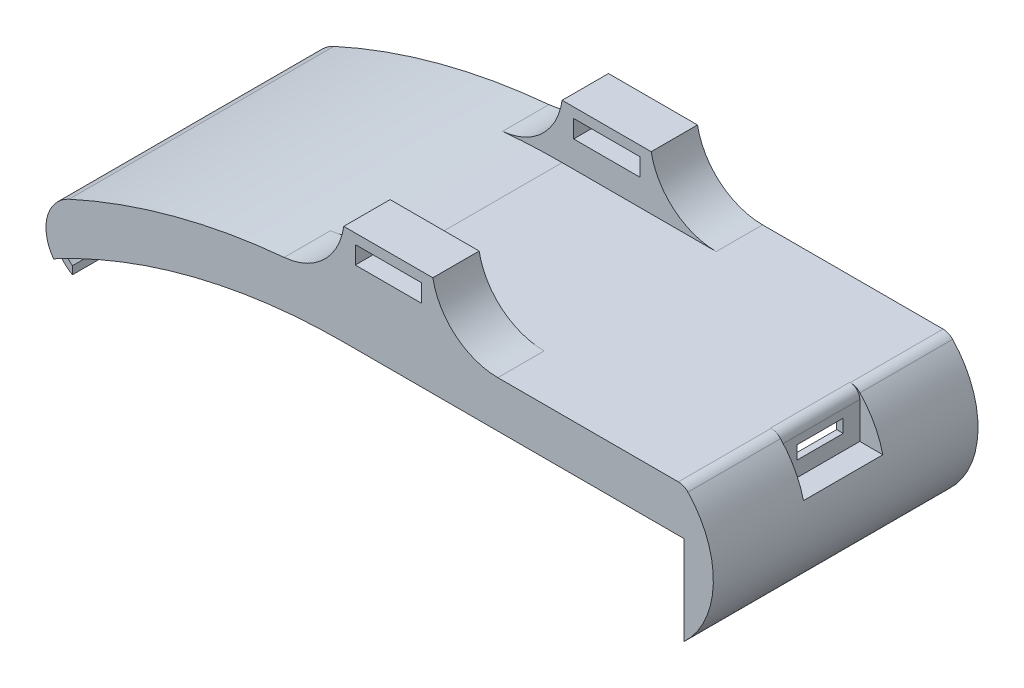
SolidWorks part; units mm, degrees
material "PLA"
ref_plane "Front Plane" through (0, 0, 0) normal (0, 0, 1) x (1, 0, 0)
ref_plane "Top Plane" through (0, 0, 0) normal (0, 1, 0) x (1, 0, 0)
ref_plane "Right Plane" through (0, 0, 0) normal (1, 0, 0) x (0, 0, -1)
sketch "Sketch1" plane through (0, 0, 0) normal (0, 0, 1) x (1, 0, 0)
  line L0 (93.6716, -39.9694) -> (93.6716, -40.9694)
  line L1 (3.6716, -40.9694) -> (3.6716, -39.9694)
  line L2 (3.6716, -39.9694) -> (-32.9868, -39.9694) construction
  line L3 (93.6716, -40.9694) -> (94.0742, -40.9694)
  line L4 (93.6271, -20.4794) -> (94.053, -20.4794)
  line L7 (93.6516, -21.4794) -> (42.6716, -21.4794)
  line L8 (93.6482, -40.9694) -> (93.6716, -40.9694)
  line L9 (93.6271, -20.4794) -> (42.6716, -20.4794)
  line L17 (93.6482, -40.9694) -> (3.6716, -40.9694) construction
  line L19 (93.6716, -39.9694) -> (3.6716, -39.9694) construction
  arc A0 (93.6516, -21.4794) -> (93.6716, -39.9694) centre (94.1163, -30.7239) cw construction
  arc A1 (42.6716, -21.4794) -> (1.5932, -30.4219) centre (42.6716, -120.3004) ccw
  arc A2 (1.5932, -30.4219) -> (3.6716, -39.9694) centre (3.6716, -34.9694) ccw
  arc A3 (93.6271, -20.4794) -> (93.6482, -40.9694) centre (94.1163, -30.7239) cw construction
  arc A4 (1.1775, -29.5124) -> (3.6716, -40.9694) centre (3.6716, -34.9694) ccw
  arc A5 (42.6716, -20.4794) -> (1.1775, -29.5124) centre (42.6716, -120.3004) ccw
  arc A6 (93.6516, -21.4794) -> (93.6716, -39.9694) centre (94.1163, -30.7239) cw construction
  arc A7 (93.6716, -39.9694) -> (93.6516, -21.4794) centre (84.5221, -30.7343) ccw
  arc A8 (94.0742, -40.9694) -> (94.053, -20.4794) centre (84.5221, -30.7343) ccw
  arc A9 (94.3754, -40.6798) -> (94.3539, -20.7675) centre (84.5221, -30.7343) ccw construction
  dimension "D9" = 5
  dimension "D6" = 13
  dimension "D2" = 1
  dimension "D3" = 50.98
  dimension "D4" = 19.49
  dimension "D5" = 90
  dimension "D7" = 1
  dimension "D8" = 39
  dimension "D1" = 1
extrude "Boss-Extrude1" add sketch "Sketch1" along normal blind 38 contours L9 A5 A4 A2 A1 L7 A0 L8 A3 region at (97.6251, -30.7201, 0)
sketch "Sketch2" plane through (0, 0, 0) normal (0, 0, -1) x (-1, 0, 0)
  line L0 (-93.6716, -40.9694) -> (-3.6716, -40.9694)
  line L6 (-93.6716, -40.9694) -> (-93.6716, -39.9694)
  line L7 (-94.0742, -40.9694) -> (-93.6716, -40.9694)
  line L8 (-42.6716, -20.4794) -> (-94.053, -20.4794)
  line L9 (-94.0742, -40.9694) -> (-93.6716, -40.9694)
  line L10 (-3.6716, -39.9694) -> (-3.6716, -40.9694)
  line L12 (-93.6516, -21.4794) -> (-42.6716, -21.4794)
  line L16 (-42.6716, -20.4794) -> (-94.053, -20.4794)
  arc A6 (-93.6516, -21.4794) -> (-93.6716, -39.9694) centre (-84.5221, -30.7343) ccw
  arc A8 (-1.5932, -30.4219) -> (-42.6716, -21.4794) centre (-42.6716, -120.3004) ccw
  arc A9 (-3.6716, -39.9694) -> (-1.5932, -30.4219) centre (-3.6716, -34.9694) ccw
  arc A10 (-3.6716, -40.9694) -> (-1.1775, -29.5124) centre (-3.6716, -34.9694) ccw
  arc A11 (-1.1775, -29.5124) -> (-42.6716, -20.4794) centre (-42.6716, -120.3004) ccw
  arc A12 (-94.053, -20.4794) -> (-94.0742, -40.9694) centre (-84.5221, -30.7343) ccw
  arc A13 (-94.053, -20.4794) -> (-94.0742, -40.9694) centre (-84.5221, -30.7343) ccw
  arc A16 (-3.6716, -40.9694) -> (-1.1775, -29.5124) centre (-3.6716, -34.9694) ccw
  arc A17 (-1.1775, -29.5124) -> (-42.6716, -20.4794) centre (-42.6716, -120.3004) ccw
  dimension "D1" = 0
extrude "Boss-Extrude2" add sketch "Sketch2" along normal blind 1
ref_plane "Plane1" through (0, 0, 19) normal (0, 0, 1) x (1, 0, 0)
mirror "Mirror1" about plane through (0, 0, 19) normal (0, 0, 1) of "Boss-Extrude2"
sketch "Sketch5" plane through (0, -21.4794, 0) normal (0, -1, 0) x (1, 0, 0)
  line L0 (42.6716, 38) -> (42.6716, 0) construction
  line L1 (45.3016, 27.89) -> (45.3016, 10.11) construction
  circle A0 centre (45.3016, 27.89) radius 1.5
  circle A1 centre (45.3016, 10.11) radius 1.5
  circle A2 centre (91.0216, 27.89) radius 1.5
  circle A3 centre (91.0216, 10.11) radius 1.5
  point P6 (42.6716, 19)
  point P7 (45.3016, 19)
  dimension "D3" = 3
  dimension "D1" = 2.63
  dimension "D2" = 17.78
  dimension "D4" = 2
extrude "Boss-Extrude4" add sketch "Sketch5" along normal blind 2
sketch "Sketch6" plane through (0.0001, -40.9694, 0) normal (0, -1, 0) x (1, 0, 0)
  line L0 (3.6715, 38) -> (3.6715, 0) construction
  line L2 (3.6715, 31.5) -> (-0.3285, 31.5)
  line L3 (3.6715, 31.5) -> (3.6715, 6.5)
  line L4 (3.6715, 6.5) -> (-0.3285, 6.5)
  line L5 (-0.3285, 31.5) -> (-0.3285, 6.5)
  point P6 (3.6715, 19)
  point P7 (-0.3285, 19)
  dimension "D1" = 25
  dimension "D2" = 4
extrude "Cut-Extrude1" cut sketch "Sketch6" against normal up to next
ref_plane "Plane2" through (98.5221, 0, 0) normal (1, 0, 0) x (0, 0, -1)
sketch "Sketch7" plane through (98.5221, 0, 0) normal (1, 0, 0) x (0, 0, -1)
  line L1 (-25, -20.4794) -> (-13, -20.4794)
  line L2 (-25, -20.4794) -> (-25, -27.4794)
  line L3 (-25, -27.4794) -> (-13, -27.4794)
  line L4 (-13, -20.4794) -> (-13, -27.4794)
  line L5 (-39, -20.4794) -> (1, -20.4794) construction
  point P7 (-19, -20.4794)
  dimension "D1" = 12
  dimension "D2" = 7
extrude "Cut-Extrude2" cut sketch "Sketch7" against normal up to vertex (4.8705 mm away) up to point (93.6516, -21.4794, 0)
sketch "Sketch8" plane through (93.6516, 0, 0) normal (1, 0, 0) x (0, 0, -1)
  line L0 (-13, -27.4794) -> (-25, -27.4794) construction
  line L1 (-13, -20.4794) -> (-13, -27.4794) construction
  line L2 (-25, -27.4794) -> (-25, -20.4794) construction
  line L3 (-13, -20.4794) -> (-13, -27.4794) construction
  line L4 (-25, -27.4794) -> (-25, -20.4794) construction
  line L5 (-25, -27.4794) -> (-13, -27.4794) construction
  line L6 (-12, -20.4794) -> (-12, -28.4794)
  line L7 (-26, -28.4794) -> (-12, -28.4794)
  line L8 (-26, -28.4794) -> (-26, -20.4794)
  line L9 (-26, -20.4794) -> (-12, -20.4794)
  line L11 (-22.5, -23.1794) -> (-15.5, -23.1794)
  line L12 (-22.5, -23.1794) -> (-22.5, -25.1794)
  line L13 (-22.5, -25.1794) -> (-15.5, -25.1794)
  line L14 (-15.5, -23.1794) -> (-15.5, -25.1794)
  line L15 (-13, -20.4794) -> (1, -20.4794) construction
  point P12 (-19, -23.1794)
  point P13 (-19, -20.4794)
  dimension "D2" = 7
  dimension "D3" = 2
  dimension "D4" = 2.7
  dimension "D1" = 1
extrude "Boss-Extrude5" add sketch "Sketch8" along normal blind 1
sketch "Sketch9" plane through (0, 0, 26) normal (0, 0, 1) x (1, 0, 0)
  line L2 (94.6516, -21.0702) -> (94.6516, -20.4794)
  line L3 (94.6516, -20.4794) -> (94.053, -20.4794)
  line L4 (94.6516, -21.0702) -> (94.6516, -20.4794)
  line L5 (94.6516, -20.4794) -> (94.053, -20.4794)
  arc A1 (94.6516, -21.0702) -> (94.053, -20.4794) centre (84.5221, -30.7343) ccw
  arc A2 (94.6516, -21.0702) -> (94.053, -20.4794) centre (84.5221, -30.7343) ccw
  dimension "D1" = 0
extrude "Cut-Extrude3" cut sketch "Sketch9" against normal up to next
sketch "Sketch10" plane through (94.6516, 0, 0) normal (1, 0, 0) x (0, 0, -1)
  line L0 (-26, -22.586) -> (-26, -28.4794) construction
  line L1 (-26, -28.4794) -> (-12, -28.4794) construction
  line L2 (-12, -28.4794) -> (-12, -22.586) construction
  line L3 (-26, -22.586) -> (-26, -28.4794)
  line L4 (-26, -28.4794) -> (-12, -28.4794)
  line L5 (-12, -28.4794) -> (-12, -22.586)
  line L6 (-25, -22.586) -> (-25, -27.4794)
  line L7 (-25, -27.4794) -> (-13, -27.4794)
  line L8 (-13, -27.4794) -> (-13, -22.586)
  line L9 (-26, -22.586) -> (-25, -22.586)
  line L10 (-12, -22.586) -> (-13, -22.586)
  dimension "D1" = 1
extrude "Boss-Extrude6" add sketch "Sketch10" along normal up to next
fillet "Fillet1" radius 2 1 edges at (94.053, -20.4794, 19)
fillet "Fillet2" radius 1.5 2 edges at (93.6516, -28.4794, 19) (94.6516, -21.0709, 19)
sketch "Sketch11" plane through (0, 0, 39) normal (0, 0, 1) x (1, 0, 0)
  line L1 (94.0742, -40.9694) -> (94.0742, -27.4794)
  line L2 (42.6716, -27.4794) -> (93.2317, -27.4794)
  line L3 (42.6716, -27.4794) -> (94.0742, -27.4794)
  line L4 (94.0742, -40.9694) -> (3.6716, -40.9694) construction
  line L5 (94.0742, -40.9694) -> (3.6716, -40.9694)
  arc A1 (1.1775, -29.5124) -> (3.6716, -40.9694) centre (3.6716, -34.9694) ccw construction
  arc A2 (42.6716, -27.4794) -> (4.0873, -35.8789) centre (42.6716, -120.3004) ccw
  arc A3 (42.6716, -27.4794) -> (-1.1844, -38.4934) centre (42.6716, -120.3004) ccw
  arc A4 (-1.1844, -38.4934) -> (3.6716, -40.9694) centre (3.6716, -34.9694) ccw
  dimension "D1" = 7
extrude "Cut-Extrude4" cut sketch "Sketch11" against normal up to surface (1 mm away) up to face at (47.448, -33.4117, 38)
sketch "Sketch12" plane through (0, 0, 38) normal (0, 0, 1) x (1, 0, 0)
  line L0 (0.6716, -40.1656) -> (0.6716, -38.9694)
  line L1 (3.6716, -40.9694) -> (3.6716, -39.9694)
  line L2 (3.6716, -40.9694) -> (3.6716, -39.9694)
  line L3 (-0.3284, -37.9694) -> (-0.3284, -39.4415) construction
  arc A3 (-0.2899, -38.0201) -> (3.6716, -39.9694) centre (3.6716, -34.9694) ccw
  arc A4 (-0.2899, -38.0201) -> (-1.1844, -38.4934) centre (42.6716, -120.3004) ccw
  arc A5 (-1.1844, -38.4934) -> (3.6716, -40.9694) centre (3.6716, -34.9694) ccw
  arc A6 (0.6716, -38.9694) -> (3.6716, -39.9694) centre (3.6716, -34.9694) ccw
  arc A8 (0.6716, -40.1656) -> (3.6716, -40.9694) centre (3.6716, -34.9694) ccw
  dimension "D2" = 1
  dimension "D1" = 0
extrude "Cut-Extrude5" cut sketch "Sketch12" against normal through all both and the other way through all
sketch "Sketch13" plane through (0, 0, -1) normal (0, 0, -1) x (-1, 0, 0)
  line L0 (-94.0742, -27.4794) -> (-94.0742, -39.5523) construction
  line L1 (-42.6716, -27.4794) -> (-94.0742, -27.4794) construction
  line L2 (-94.0742, -27.4794) -> (-94.0742, -40.9694)
  line L3 (-42.6716, -27.4794) -> (-94.0742, -27.4794)
  line L4 (-94.0742, -40.9694) -> (-3.6716, -40.9694) construction
  line L6 (-3.6716, -40.9694) -> (-3.6716, -39.9694) construction
  line L7 (-3.6716, -40.9694) -> (-3.6716, -39.9694)
  line L8 (-94.0742, -40.9694) -> (-3.6716, -40.9694)
  line L9 (-0.6716, -38.9694) -> (-0.6716, -40.1656) construction
  line L10 (-0.6716, -38.9694) -> (-0.6716, -40.1656)
  arc A0 (0.2899, -38.0201) -> (-42.6716, -27.4794) centre (-42.6716, -120.3004) ccw construction
  arc A1 (1.1844, -38.4934) -> (-42.6716, -27.4794) centre (-42.6716, -120.3004) ccw
  arc A2 (-0.6716, -40.1656) -> (-1.1775, -29.5124) centre (-3.6716, -34.9694) ccw construction
  arc A3 (-3.6716, -39.9694) -> (-0.6716, -38.9694) centre (-3.6716, -34.9694) ccw construction
  arc A4 (-3.6716, -39.9694) -> (-0.6716, -38.9694) centre (-3.6716, -34.9694) ccw
  arc A5 (-0.6716, -40.1656) -> (1.1844, -38.4934) centre (-3.6716, -34.9694) ccw
extrude "Cut-Extrude6" cut sketch "Sketch13" against normal up to surface (1 mm away) up to face at (41.7676, -33.9994, 0)
sketch "Sketch14" plane through (0, 0, 39) normal (0, 0, 1) x (1, 0, 0)
  line L7 (42.6716, -20.4794) -> (42.6716, -12.3197)
  line L8 (44.4144, -16.5128) -> (44.4144, -13.8278)
  line L9 (54.4318, -16.5128) -> (44.4144, -16.5128)
  line L10 (54.4318, -13.8278) -> (54.4318, -16.5128)
  line L11 (44.4144, -13.8278) -> (54.4318, -13.8278)
  line L12 (42.6716, -12.3197) -> (56.1306, -12.3197)
  line L13 (56.1306, -12.3197) -> (56.1306, -20.4794)
  line L15 (42.6716, -20.4794) -> (56.1306, -20.4794)
extrude "Boss-Extrude7" add sketch "Sketch14" against normal blind 7
sketch "Sketch15" plane through (0, 0, -1) normal (0, 0, -1) x (-1, 0, 0)
  line L0 (-44.4144, -13.8278) -> (-44.4144, -16.5128) construction
  line L1 (-44.4144, -16.5128) -> (-54.4318, -16.5128) construction
  line L2 (-54.4318, -13.8278) -> (-44.4144, -13.8278) construction
  line L3 (-54.4318, -16.5128) -> (-54.4318, -13.8278) construction
  line L4 (-56.1306, -20.4794) -> (-42.6716, -20.4794)
  line L5 (-56.1306, -20.4794) -> (-42.6716, -20.4794)
  line L6 (-42.6716, -20.4794) -> (-42.6716, -12.3197)
  line L7 (-42.6716, -20.4794) -> (-42.6716, -12.3197)
  line L8 (-42.6716, -12.3197) -> (-56.1306, -12.3197)
  line L9 (-42.6716, -12.3197) -> (-56.1306, -12.3197)
  line L10 (-56.1306, -12.3197) -> (-56.1306, -20.4794)
  line L11 (-56.1306, -12.3197) -> (-56.1306, -20.4794)
  line L12 (-44.4144, -13.8278) -> (-44.4144, -16.5128)
  line L13 (-44.4144, -16.5128) -> (-54.4318, -16.5128)
  line L14 (-54.4318, -13.8278) -> (-44.4144, -13.8278)
  line L15 (-54.4318, -16.5128) -> (-54.4318, -13.8278)
  line L20 (-42.6716, -20.4794) -> (-56.1306, -20.4794) construction
  line L21 (-42.6716, -12.3197) -> (-42.6716, -20.4794) construction
  line L22 (-56.1306, -12.3197) -> (-42.6716, -12.3197) construction
  line L23 (-56.1306, -20.4794) -> (-56.1306, -12.3197) construction
  line L24 (-42.6716, -20.4794) -> (-56.1306, -20.4794)
  line L25 (-42.6716, -12.3197) -> (-42.6716, -20.4794)
  line L26 (-56.1306, -12.3197) -> (-42.6716, -12.3197)
  line L27 (-56.1306, -20.4794) -> (-56.1306, -12.3197)
  line M8 (-42.6716, -20.4794) -> (-93.2317, -20.4794)
  dimension "D1" = 0
extrude "Boss-Extrude8" add sketch "Sketch15" against normal blind 7 contours L27 L25 L26 M8 region at (49.394, -16.7983, -1)
fillet "Fillet3" radius 10 4 edges at (56.1306, -20.4794, 35.5) (42.6716, -20.4794, 35.5) (42.6716, -20.4794, 2.5) (56.1306, -20.4794, 2.5)
